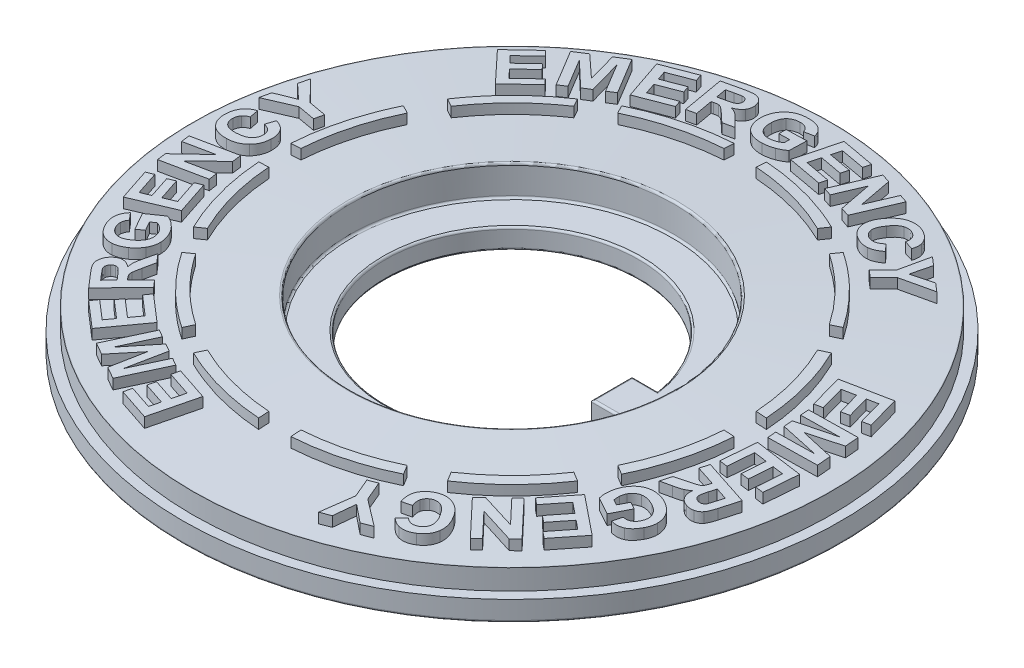
SolidWorks part; units mm, degrees
ref_plane "Front Plane" through (0, 0, 0) normal (0, 0, 1) x (1, 0, 0)
ref_plane "Top Plane" through (0, 0, 0) normal (0, 1, 0) x (1, 0, 0)
ref_plane "Right Plane" through (0, 0, 0) normal (1, 0, 0) x (0, 0, -1)
sketch "Sketch1" plane through (0, 0, 0) normal (0, 1, 0) x (1, 0, 0)
  circle A0 centre (0, 0) radius 12.5
  circle A1 centre (0, 0) radius 32.5
  dimension "D1" = 25
  dimension "D2" = 65
extrude "Boss-Extrude1" add sketch "Sketch1" along normal blind 2
sketch "Sketch2" plane through (0, 2, 0) normal (0, 1, 0) x (1, 0, 0)
  circle A1 centre (0, 0) radius 16
  circle A3 centre (0, 0) radius 31.5
  circle A4 centre (0, 0) radius 31.5
  dimension "D1" = 32
  dimension "D2" = 1
extrude "Boss-Extrude2" add sketch "Sketch2" along normal blind 3
sketch "Sketch3" plane through (0, 0, 0) normal (0, 0, 1) x (1, 0, 0)
  line L0 (15.9676, 5) -> (31.4687, 4)
  line L1 (16, 5) -> (-16, 5) construction
  line L2 (31.4687, 4) -> (33.9142, 4)
  line L3 (33.9142, 4) -> (33.9142, 6.9871)
  line L4 (33.9142, 6.9871) -> (15.9676, 6.9871)
  line L5 (15.9676, 6.9871) -> (15.9676, 5)
  line L6 (31.5, 5) -> (-31.5, 5) construction
  dimension "D1" = 1
revolve "Cut-Revolve1" cut sketch "Sketch3" angle 360 about axis through (0, 5, 0) along (0, -1, 0)
sketch "Sketch4" plane through (0, 0, 0) normal (0, -1, 0) x (1, 0, 0)
  line L0 (0, 0) -> (14.9309, 0) construction
  line L1 (12.339, 0) -> (12.339, -2) construction
  line L2 (12.339, 2) -> (13.461, 2)
  line L3 (12.339, -2) -> (9.839, -2)
  line L4 (13.461, 2) -> (13.461, -2)
  line L5 (12.339, 2) -> (9.839, 2)
  line L6 (9.839, -2) -> (9.839, 2)
  line L7 (13.461, -2) -> (12.339, -2)
  circle A0 centre (0, 0) radius 12.5 construction
  circle A1 centre (0, 0) radius 12.5 construction
  dimension "D1" = 2
  dimension "D2" = 4
  dimension "D3" = 2.5
extrude "Boss-Extrude3" add sketch "Sketch4" against normal up to surface (2 mm away) up to face at (0, 2, 12.5)
fillet "Fillet1" radius 0.2 12 edges at (0, 4, 31.4687) (0, 4.9979, -16) (11.089, 0, -2) (9.839, 0, 0) (11.089, 0, 2) (-12.5, 0, 0) (0, 0, 32.5) (0, 2, 16) (9.839, 2, 0) (11.089, 2, -2) (-12.5, 2, 0) (11.089, 2, 2)
sketch "Sketch5" plane through (0, 0, 0) normal (0, 1, 0) x (1, 0, 0)
  line L0 (-6.1951, -24.2972) -> (-7.6292, -28.6092)
  line L1 (-7.6292, -28.6092) -> (-10.8269, -27.5469)
  line L2 (-10.8269, -27.5469) -> (-10.5843, -26.8175)
  line L3 (-10.5843, -26.8175) -> (-8.2571, -27.5902)
  line L4 (-8.2571, -27.5902) -> (-7.9394, -26.635)
  line L5 (-7.9394, -26.635) -> (-10.1044, -25.9142)
  line L6 (-10.1044, -25.9142) -> (-9.8628, -25.1879)
  line L7 (-9.8628, -25.1879) -> (-7.6977, -25.9076)
  line L8 (-7.6977, -25.9076) -> (-7.3082, -24.7339)
  line L9 (-7.3082, -24.7339) -> (-9.7171, -23.933)
  line L10 (-9.7171, -23.933) -> (-9.4755, -23.2067)
  line L11 (-9.4755, -23.2067) -> (-6.1951, -24.2972)
  line L12 (-10.2124, -22.9447) -> (-12.4691, -26.8859)
  line L13 (-12.4691, -26.8859) -> (-13.6598, -26.2044)
  line L14 (-13.6598, -26.2044) -> (-12.8357, -23.1061)
  line L15 (-12.8357, -23.1061) -> (-15.0816, -25.3898)
  line L16 (-15.0816, -25.3898) -> (-16.2744, -24.7062)
  line L17 (-16.2744, -24.7062) -> (-14.0178, -20.7662)
  line L18 (-14.0178, -20.7662) -> (-13.2794, -21.1892)
  line L19 (-13.2794, -21.1892) -> (-15.055, -24.2913)
  line L20 (-15.055, -24.2913) -> (-12.4965, -21.6366)
  line L21 (-12.4965, -21.6366) -> (-11.7305, -22.0754)
  line L22 (-11.7305, -22.0754) -> (-12.7275, -25.6237)
  line L23 (-12.7275, -25.6237) -> (-10.9519, -22.5217)
  line L24 (-10.9519, -22.5217) -> (-10.2124, -22.9447)
  line L25 (-14.7736, -20.2293) -> (-17.7469, -23.6613)
  line L26 (-17.7469, -23.6613) -> (-20.2918, -21.457)
  line L27 (-20.2918, -21.457) -> (-19.7891, -20.8761)
  line L28 (-19.7891, -20.8761) -> (-17.9373, -22.4805)
  line L29 (-17.9373, -22.4805) -> (-17.2782, -21.7195)
  line L30 (-17.2782, -21.7195) -> (-19.0017, -20.2271)
  line L31 (-19.0017, -20.2271) -> (-18.5, -19.6483)
  line L32 (-18.5, -19.6483) -> (-16.7765, -21.1408)
  line L33 (-16.7765, -21.1408) -> (-15.9674, -20.207)
  line L34 (-15.9674, -20.207) -> (-17.8849, -18.5456)
  line L35 (-17.8849, -18.5456) -> (-17.3841, -17.9679)
  line L36 (-17.3841, -17.9679) -> (-14.7736, -20.2293)
  line L37 (-17.9353, -17.4044) -> (-21.3725, -20.3714)
  line L38 (-21.3725, -20.3714) -> (-22.6337, -18.9108)
  line L39 (-20.9108, -15.3133) -> (-20.6033, -14.3148)
  line L40 (-20.6033, -14.3148) -> (-19.8861, -15.1447)
  line L41 (-19.8861, -15.1447) -> (-20.2014, -16.2914)
  line L42 (-20.0907, -17.8082) -> (-19.9693, -17.9492)
  line L43 (-19.9693, -17.9492) -> (-18.5352, -16.7102)
  line L44 (-18.5352, -16.7102) -> (-17.9353, -17.4044)
  line L45 (-20.5183, -18.4224) -> (-20.9609, -17.9093)
  line L46 (-21.8574, -18.6338) -> (-21.3906, -19.1754)
  line L47 (-21.3906, -19.1754) -> (-20.5183, -18.4224)
  line L48 (-23.3127, -12.83) -> (-23.977, -13.2097)
  line L49 (-23.977, -13.2097) -> (-24.9571, -11.4924)
  line L50 (-24.9571, -11.4924) -> (-23.3849, -10.5967)
  line L51 (-25.6649, -11.9642) -> (-25.0651, -12.6712)
  line L52 (-23.3328, -11.6329) -> (-23.8329, -11.9178)
  line L53 (-23.8329, -11.9178) -> (-23.3127, -12.83)
  line L54 (-23.1179, -9.4693) -> (-27.4298, -10.895)
  line L55 (-27.4298, -10.895) -> (-28.4868, -7.6974)
  line L56 (-28.4868, -7.6974) -> (-27.7574, -7.4558)
  line L57 (-27.7574, -7.4558) -> (-26.9888, -9.7829)
  line L58 (-26.9888, -9.7829) -> (-26.0326, -9.4663)
  line L59 (-26.0326, -9.4663) -> (-26.748, -7.3014)
  line L60 (-26.748, -7.3014) -> (-26.0217, -7.0618)
  line L61 (-26.0217, -7.0618) -> (-25.3063, -9.2269)
  line L62 (-25.3063, -9.2269) -> (-24.1326, -8.8384)
  line L63 (-24.1326, -8.8384) -> (-24.9293, -6.4295)
  line L64 (-24.9293, -6.4295) -> (-24.2019, -6.189)
  line L65 (-24.2019, -6.189) -> (-23.1179, -9.4693)
  line L66 (-24.437, -5.4222) -> (-28.9431, -6.0107)
  line L67 (-28.9431, -6.0107) -> (-29.059, -5.1253)
  line L68 (-29.059, -5.1253) -> (-26.2903, -2.8879)
  line L69 (-26.2903, -2.8879) -> (-29.2997, -3.2817)
  line L70 (-29.2997, -3.2817) -> (-29.4102, -2.4354)
  line L71 (-29.4102, -2.4354) -> (-24.9041, -1.8469)
  line L72 (-24.9041, -1.8469) -> (-24.7849, -2.7598)
  line L73 (-24.7849, -2.7598) -> (-27.486, -4.961)
  line L74 (-27.486, -4.961) -> (-24.5476, -4.577)
  line L75 (-24.5476, -4.577) -> (-24.437, -5.4222)
  line L76 (-26.513, 2.089) -> (-26.2014, 2.9683)
  line L77 (-28.1029, 3.0201) -> (-27.9174, 2.1053)
  line L78 (-24.4491, 4.8765) -> (-26.3129, 5.3062)
  line L79 (-26.3129, 5.3062) -> (-29.2507, 4.2763)
  line L80 (-29.2507, 4.2763) -> (-29.0095, 5.324)
  line L81 (-29.0095, 5.324) -> (-27.0166, 5.9623)
  line L82 (-27.0166, 5.9623) -> (-28.5333, 7.3868)
  line L83 (-28.5333, 7.3868) -> (-28.2952, 8.4165)
  line L84 (-28.2952, 8.4165) -> (-26.1012, 6.1962)
  line L85 (-26.1012, 6.1962) -> (-24.2438, 5.7676)
  line L86 (-24.2438, 5.7676) -> (-24.4491, 4.8765)
  line L87 (-18.4634, 16.8285) -> (-21.5758, 20.1391)
  line L88 (-21.5758, 20.1391) -> (-19.1203, 22.4473)
  line L89 (-19.1203, 22.4473) -> (-18.5936, 21.8872)
  line L90 (-18.5936, 21.8872) -> (-20.3804, 20.2076)
  line L91 (-20.3804, 20.2076) -> (-19.6909, 19.4739)
  line L92 (-19.6909, 19.4739) -> (-18.0287, 21.0368)
  line L93 (-18.0287, 21.0368) -> (-17.5041, 20.4789)
  line L94 (-17.5041, 20.4789) -> (-19.1664, 18.9159)
  line L95 (-19.1664, 18.9159) -> (-18.3192, 18.015)
  line L96 (-18.3192, 18.015) -> (-16.4696, 19.7536)
  line L97 (-16.4696, 19.7536) -> (-15.945, 19.1956)
  line L98 (-15.945, 19.1956) -> (-18.4634, 16.8285)
  line L99 (-15.393, 19.7468) -> (-17.8185, 23.588)
  line L100 (-17.8185, 23.588) -> (-16.6575, 24.3209)
  line L101 (-16.6575, 24.3209) -> (-14.3069, 22.1408)
  line L102 (-14.3069, 22.1408) -> (-15.2712, 25.1954)
  line L103 (-15.2712, 25.1954) -> (-14.1081, 25.9306)
  line L104 (-14.1081, 25.9306) -> (-11.6825, 22.0894)
  line L105 (-11.6825, 22.0894) -> (-12.4038, 21.6344)
  line L106 (-12.4038, 21.6344) -> (-14.3123, 24.6575)
  line L107 (-14.3123, 24.6575) -> (-13.1665, 21.153)
  line L108 (-13.1665, 21.153) -> (-13.9132, 20.6811)
  line L109 (-13.9132, 20.6811) -> (-16.5823, 23.2251)
  line L110 (-16.5823, 23.2251) -> (-14.6728, 20.2018)
  line L111 (-14.6728, 20.2018) -> (-15.393, 19.7468)
  line L112 (-10.8729, 22.5268) -> (-12.502, 26.7677)
  line L113 (-12.502, 26.7677) -> (-9.3579, 27.9763)
  line L114 (-9.3579, 27.9763) -> (-9.0825, 27.2585)
  line L115 (-9.0825, 27.2585) -> (-11.3707, 26.3793)
  line L116 (-11.3707, 26.3793) -> (-11.0093, 25.4395)
  line L117 (-11.0093, 25.4395) -> (-8.8803, 26.2577)
  line L118 (-8.8803, 26.2577) -> (-8.6048, 25.5431)
  line L119 (-8.6048, 25.5431) -> (-10.7347, 24.7249)
  line L120 (-10.7347, 24.7249) -> (-10.2915, 23.5708)
  line L121 (-10.2915, 23.5708) -> (-7.9215, 24.4811)
  line L122 (-7.9215, 24.4811) -> (-7.6471, 23.7665)
  line L123 (-7.6471, 23.7665) -> (-10.8729, 22.5268)
  line L124 (-6.9043, 24.0185) -> (-7.918, 28.4456)
  line L125 (-7.918, 28.4456) -> (-6.0364, 28.8762)
  line L126 (-3.6626, 25.6705) -> (-2.9239, 24.9296)
  line L127 (-2.9239, 24.9296) -> (-3.9929, 24.6852)
  line L128 (-3.9929, 24.6852) -> (-4.8596, 25.5011)
  line L129 (-6.2523, 26.113) -> (-6.4334, 26.0717)
  line L130 (-6.4334, 26.0717) -> (-6.01, 24.2227)
  line L131 (-6.01, 24.2227) -> (-6.9043, 24.0185)
  line L132 (-6.5952, 26.7786) -> (-5.9338, 26.9299)
  line L133 (-6.1549, 28.0613) -> (-6.8524, 27.9015)
  line L134 (-6.8524, 27.9015) -> (-6.5952, 26.7786)
  line L135 (-0.3471, 26.653) -> (-0.3722, 27.418)
  line L136 (-0.3722, 27.418) -> (1.6033, 27.4821)
  line L137 (1.6033, 27.4821) -> (1.6619, 25.6727)
  line L138 (1.5173, 28.3281) -> (0.6119, 28.1285)
  line L139 (0.7208, 26.111) -> (0.7025, 26.6866)
  line L140 (0.7025, 26.6866) -> (-0.3471, 26.653)
  line L141 (2.5402, 24.9255) -> (3.3541, 29.3962)
  line L142 (3.3541, 29.3962) -> (6.6696, 28.7922)
  line L143 (6.6696, 28.7922) -> (6.5315, 28.0358)
  line L144 (6.5315, 28.0358) -> (4.1194, 28.476)
  line L145 (4.1194, 28.476) -> (3.9384, 27.4847)
  line L146 (3.9384, 27.4847) -> (6.1834, 27.0757)
  line L147 (6.1834, 27.0757) -> (6.0463, 26.3223)
  line L148 (6.0463, 26.3223) -> (3.8013, 26.7314)
  line L149 (3.8013, 26.7314) -> (3.5797, 25.5137)
  line L150 (3.5797, 25.5137) -> (6.0775, 25.0587)
  line L151 (6.0775, 25.0587) -> (5.9403, 24.3055)
  line L152 (5.9403, 24.3055) -> (2.5402, 24.9255)
  line L153 (6.711, 24.1235) -> (8.1441, 28.4356)
  line L154 (8.1441, 28.4356) -> (8.9911, 28.1544)
  line L155 (8.9911, 28.1544) -> (9.7993, 24.6873)
  line L156 (9.7993, 24.6873) -> (10.7564, 27.568)
  line L157 (10.7564, 27.568) -> (11.5654, 27.2982)
  line L158 (11.5654, 27.2982) -> (10.1313, 22.9862)
  line L159 (10.1313, 22.9862) -> (9.2576, 23.2768)
  line L160 (9.2576, 23.2768) -> (8.4541, 26.6666)
  line L161 (8.4541, 26.6666) -> (7.5199, 23.8548)
  line L162 (7.5199, 23.8548) -> (6.711, 24.1235)
  line L163 (14.3535, 22.5323) -> (14.9855, 21.8455)
  line L164 (15.9191, 23.5025) -> (15.0244, 23.7654)
  line L165 (15.8425, 19.3835) -> (17.0931, 20.8283)
  line L166 (17.0931, 20.8283) -> (17.5577, 23.9046)
  line L167 (17.5577, 23.9046) -> (18.3707, 23.2011)
  line L168 (18.3707, 23.2011) -> (18.0016, 21.143)
  line L169 (18.0016, 21.143) -> (19.97, 21.8153)
  line L170 (19.97, 21.8153) -> (20.7682, 21.1234)
  line L171 (20.7682, 21.1234) -> (17.7799, 20.225)
  line L172 (17.7799, 20.225) -> (16.5325, 18.7846)
  line L173 (16.5325, 18.7846) -> (15.8425, 19.3835)
  line L174 (23.6341, 8.518) -> (28.0103, 9.744)
  line L175 (28.0103, 9.744) -> (28.9196, 6.5001)
  line L176 (28.9196, 6.5001) -> (28.1793, 6.2924)
  line L177 (28.1793, 6.2924) -> (27.5175, 8.6531)
  line L178 (27.5175, 8.6531) -> (26.5474, 8.3815)
  line L179 (26.5474, 8.3815) -> (27.163, 6.1849)
  line L180 (27.163, 6.1849) -> (26.4259, 5.9783)
  line L181 (26.4259, 5.9783) -> (25.8102, 8.1748)
  line L182 (25.8102, 8.1748) -> (24.6188, 7.8413)
  line L183 (24.6188, 7.8413) -> (25.3036, 5.3969)
  line L184 (25.3036, 5.3969) -> (24.5665, 5.1903)
  line L185 (24.5665, 5.1903) -> (23.6341, 8.518)
  line L186 (24.8024, 4.4417) -> (29.332, 4.8102)
  line L187 (29.332, 4.8102) -> (29.443, 3.4425)
  line L188 (29.443, 3.4425) -> (26.4207, 2.3688)
  line L189 (26.4207, 2.3688) -> (29.5759, 1.807)
  line L190 (29.5759, 1.807) -> (29.688, 0.4351)
  line L191 (29.688, 0.4351) -> (25.1584, 0.0665)
  line L192 (25.1584, 0.0665) -> (25.0886, 0.917)
  line L193 (25.0886, 0.917) -> (28.6546, 1.2066)
  line L194 (28.6546, 1.2066) -> (25.0164, 1.8162)
  line L195 (25.0164, 1.8162) -> (24.9444, 2.6962)
  line L196 (24.9444, 2.6962) -> (28.437, 3.8829)
  line L197 (28.437, 3.8829) -> (24.8711, 3.5922)
  line L198 (24.8711, 3.5922) -> (24.8024, 4.4417)
  line L199 (25.0744, -0.851) -> (29.5986, -1.2269)
  line L200 (29.5986, -1.2269) -> (29.3198, -4.5823)
  line L201 (29.3198, -4.5823) -> (28.5551, -4.5183)
  line L202 (28.5551, -4.5183) -> (28.7573, -2.0769)
  line L203 (28.7573, -2.0769) -> (27.7545, -1.9935)
  line L204 (27.7545, -1.9935) -> (27.566, -4.2656)
  line L205 (27.566, -4.2656) -> (26.8033, -4.2017)
  line L206 (26.8033, -4.2017) -> (26.9918, -1.9305)
  line L207 (26.9918, -1.9305) -> (25.7606, -1.8277)
  line L208 (25.7606, -1.8277) -> (25.5503, -4.356)
  line L209 (25.5503, -4.356) -> (24.7876, -4.292)
  line L210 (24.7876, -4.292) -> (25.0744, -0.851)
  line L211 (24.6298, -5.0707) -> (29.0007, -6.3042)
  line L212 (29.0007, -6.3042) -> (28.4763, -8.1619)
  line L213 (24.5238, -8.7075) -> (23.5212, -9.0011)
  line L214 (23.5212, -9.0011) -> (23.819, -7.9451)
  line L215 (23.819, -7.9451) -> (24.9495, -7.576)
  line L216 (26.1547, -6.647) -> (26.205, -6.468)
  line L217 (26.205, -6.468) -> (24.3802, -5.954)
  line L218 (24.3802, -5.954) -> (24.6298, -5.0707)
  line L219 (26.903, -6.6652) -> (26.7184, -7.3186)
  line L220 (27.8178, -7.6672) -> (28.0129, -6.9777)
  line L221 (28.0129, -6.9777) -> (26.903, -6.6652)
  line L222 (23.8344, -12.1172) -> (24.5142, -12.468)
  line L223 (24.5142, -12.468) -> (23.6067, -14.225)
  line L224 (23.6067, -14.225) -> (21.9987, -13.394)
  line L225 (24.3881, -14.5621) -> (24.6545, -13.6747)
  line L226 (22.8392, -12.7863) -> (23.3519, -13.0507)
  line L227 (23.3519, -13.0507) -> (23.8344, -12.1172)
  line L228 (21.0017, -13.8427) -> (24.5624, -16.6606)
  line L229 (24.5624, -16.6606) -> (22.4731, -19.3005)
  line L230 (22.4731, -19.3005) -> (21.8702, -18.8236)
  line L231 (21.8702, -18.8236) -> (23.3912, -16.9028)
  line L232 (23.3912, -16.9028) -> (22.6013, -16.2772)
  line L233 (22.6013, -16.2772) -> (21.1865, -18.0649)
  line L234 (21.1865, -18.0649) -> (20.5867, -17.5901)
  line L235 (20.5867, -17.5901) -> (22.0016, -15.8024)
  line L236 (22.0016, -15.8024) -> (21.0332, -15.0356)
  line L237 (21.0332, -15.0356) -> (19.458, -17.0249)
  line L238 (19.458, -17.0249) -> (18.8583, -16.5502)
  line L239 (18.8583, -16.5502) -> (21.0017, -13.8427)
  line L240 (18.3331, -17.1447) -> (21.4454, -20.4563)
  line L241 (21.4454, -20.4563) -> (20.7947, -21.067)
  line L242 (20.7947, -21.067) -> (17.3611, -20.1304)
  line L243 (17.3611, -20.1304) -> (19.4392, -22.3409)
  line L244 (19.4392, -22.3409) -> (18.8184, -22.9254)
  line L245 (18.8184, -22.9254) -> (15.7061, -19.6137)
  line L246 (15.7061, -19.6137) -> (16.3769, -18.9831)
  line L247 (16.3769, -18.9831) -> (19.7409, -19.8875)
  line L248 (19.7409, -19.8875) -> (17.7111, -17.7291)
  line L249 (17.7111, -17.7291) -> (18.3331, -17.1447)
  line L250 (13.3532, -23.1592) -> (12.4501, -23.3963)
  line L251 (13.4769, -24.9983) -> (14.1285, -24.33)
  line L252 (9.8859, -23.0128) -> (10.5714, -24.7977)
  line L253 (10.5714, -24.7977) -> (13.0694, -26.6571)
  line L254 (13.0694, -26.6571) -> (12.0649, -27.0435)
  line L255 (12.0649, -27.0435) -> (10.4227, -25.7479)
  line L256 (10.4227, -25.7479) -> (10.0889, -27.8026)
  line L257 (10.0889, -27.8026) -> (9.1025, -28.1817)
  line L258 (9.1025, -28.1817) -> (9.7157, -25.1197)
  line L259 (9.7157, -25.1197) -> (9.0322, -23.3411)
  line L260 (9.0322, -23.3411) -> (9.8859, -23.0128)
  line L261 (-10.275, 21.0761) -> (-9.7743, 20.2088)
  line L262 (-1.513, 22.4187) -> (-1.513, 23.4207)
  line L263 (-19.4378, 13.0737) -> (-18.5693, 12.5723)
  line L264 (-12.5224, 18.6187) -> (-13.0236, 19.4867)
  line L265 (-23.3726, 1.5627) -> (-22.3702, 1.5627)
  line L266 (-20.16, 9.8245) -> (-21.0281, 10.3256)
  line L267 (-21.0264, -10.3743) -> (-20.1591, -9.8736)
  line L268 (-22.369, -1.6123) -> (-23.371, -1.6123)
  line L269 (-13.024, -19.5371) -> (-12.5226, -18.6686)
  line L270 (-18.569, -12.6217) -> (-19.437, -13.1229)
  line L271 (-1.513, -23.4719) -> (-1.513, -22.4695)
  line L272 (-9.7748, -20.2593) -> (-10.2759, -21.1274)
  line L273 (10.424, -21.1257) -> (9.9233, -20.2584)
  line L274 (1.662, -22.4683) -> (1.662, -23.4703)
  line L275 (19.5868, -13.1233) -> (18.7183, -12.6219)
  line L276 (12.6714, -18.6683) -> (13.1726, -19.5363)
  line L277 (23.5216, -1.6123) -> (22.5192, -1.6123)
  line L278 (20.309, -9.8741) -> (21.1771, -10.3752)
  line L279 (21.1763, 10.3252) -> (20.3086, 9.8242)
  line L280 (22.5186, 1.5627) -> (23.5204, 1.5627)
  line L281 (13.1724, 19.4864) -> (12.6714, 18.6186)
  line L282 (18.7181, 12.5722) -> (19.586, 13.0733)
  line L283 (1.662, 23.4207) -> (1.662, 22.4187)
  line L284 (9.9232, 20.2086) -> (10.4243, 21.0767)
  ellipse E0 centre (0.0745, -0.0248) end of major axis (0.0745, -25.0248) minor radius 25 construction
  spline S0 degree 3 poles (-22.6337, -18.9108) (-22.9506, -18.543) (-23.15, -18.2496) (-23.2322, -18.0304) knots 0.105263 0.105263 0.105263 0.105263 0.157895 0.157895 0.157895 0.157895
  spline S1 degree 3 poles (-23.2322, -18.0304) (-23.3133, -17.8101) (-23.3193, -17.5825) (-23.2479, -17.3466) knots 0.157895 0.157895 0.157895 0.157895 0.210526 0.210526 0.210526 0.210526
  spline S2 degree 3 poles (-23.2479, -17.3466) (-23.1756, -17.1097) (-23.0388, -16.9036) (-22.8352, -16.7282) knots 0.210526 0.210526 0.210526 0.210526 0.263158 0.263158 0.263158 0.263158
  spline S3 degree 3 poles (-22.8352, -16.7282) (-22.5776, -16.5064) (-22.2992, -16.3979) (-22.0007, -16.4047) knots 0.263158 0.263158 0.263158 0.263158 0.315789 0.315789 0.315789 0.315789
  spline S4 degree 3 poles (-22.0007, -16.4047) (-21.7012, -16.4116) (-21.3998, -16.5464) (-21.0955, -16.8106) knots 0.315789 0.315789 0.315789 0.315789 0.368421 0.368421 0.368421 0.368421
  spline S5 degree 3 poles (-21.0955, -16.8106) (-21.1374, -16.585) (-21.1487, -16.3776) (-21.1283, -16.1893) knots 0.368421 0.368421 0.368421 0.368421 0.421053 0.421053 0.421053 0.421053
  spline S6 degree 3 poles (-21.1283, -16.1893) (-21.1078, -16.0019) (-21.0354, -15.71) (-20.9108, -15.3133) knots 0.421053 0.421053 0.421053 0.421053 0.473684 0.473684 0.473684 0.473684
  spline S7 degree 3 poles (-20.2014, -16.2914) (-20.3153, -16.7007) (-20.3781, -16.9684) (-20.3911, -17.0933) knots 0.631579 0.631579 0.631579 0.631579 0.684211 0.684211 0.684211 0.684211
  spline S8 degree 3 poles (-20.3911, -17.0933) (-20.404, -17.2192) (-20.3915, -17.3304) (-20.3536, -17.4257) knots 0.684211 0.684211 0.684211 0.684211 0.736842 0.736842 0.736842 0.736842
  spline S9 degree 3 poles (-20.3536, -17.4257) (-20.3156, -17.521) (-20.228, -17.6491) (-20.0907, -17.8082) knots 0.736842 0.736842 0.736842 0.736842 0.789474 0.789474 0.789474 0.789474
  spline S10 degree 3 poles (-20.9609, -17.9093) (-21.2481, -17.5765) (-21.4425, -17.3804) (-21.5419, -17.322) knots 0.1 0.1 0.1 0.1 0.2 0.2 0.2 0.2
  spline S11 degree 3 poles (-21.5419, -17.322) (-21.6413, -17.2637) (-21.746, -17.2402) (-21.8551, -17.2527) knots 0.2 0.2 0.2 0.2 0.3 0.3 0.3 0.3
  spline S12 degree 3 poles (-21.8551, -17.2527) (-21.9641, -17.2652) (-22.07, -17.3158) (-22.1739, -17.4056) knots 0.3 0.3 0.3 0.3 0.4 0.4 0.4 0.4
  spline S13 degree 3 poles (-22.1739, -17.4056) (-22.2894, -17.5048) (-22.3563, -17.617) (-22.3734, -17.7397) knots 0.4 0.4 0.4 0.4 0.5 0.5 0.5 0.5
  spline S14 degree 3 poles (-22.3734, -17.7397) (-22.3916, -17.8625) (-22.3611, -17.9885) (-22.2831, -18.1177) knots 0.5 0.5 0.5 0.5 0.6 0.6 0.6 0.6
  spline S15 degree 3 poles (-22.2831, -18.1177) (-22.2419, -18.1802) (-22.1004, -18.3529) (-21.8574, -18.6338) knots 0.6 0.6 0.6 0.6 0.7 0.7 0.7 0.7
  spline S16 degree 3 poles (-23.3849, -10.5967) (-23.1289, -10.6713) (-22.8488, -10.8316) (-22.5444, -11.0777) knots 0.12 0.12 0.12 0.12 0.16 0.16 0.16 0.16
  spline S17 degree 3 poles (-22.5444, -11.0777) (-22.2411, -11.3249) (-21.9971, -11.6099) (-21.8115, -11.9353) knots 0.16 0.16 0.16 0.16 0.2 0.2 0.2 0.2
  spline S18 degree 3 poles (-21.8115, -11.9353) (-21.5762, -12.3473) (-21.4584, -12.7572) (-21.456, -13.1625) knots 0.2 0.2 0.2 0.2 0.24 0.24 0.24 0.24
  spline S19 degree 3 poles (-21.456, -13.1625) (-21.4545, -13.5678) (-21.5706, -13.9391) (-21.804, -14.2773) knots 0.24 0.24 0.24 0.24 0.28 0.28 0.28 0.28
  spline S20 degree 3 poles (-21.804, -14.2773) (-22.0386, -14.6155) (-22.3449, -14.8922) (-22.7231, -15.1085) knots 0.28 0.28 0.28 0.28 0.32 0.32 0.32 0.32
  spline S21 degree 3 poles (-22.7231, -15.1085) (-23.1342, -15.3428) (-23.5482, -15.4648) (-23.9663, -15.4746) knots 0.32 0.32 0.32 0.32 0.36 0.36 0.36 0.36
  spline S22 degree 3 poles (-23.9663, -15.4746) (-24.3833, -15.4844) (-24.7715, -15.3716) (-25.132, -15.137) knots 0.36 0.36 0.36 0.36 0.4 0.4 0.4 0.4
  spline S23 degree 3 poles (-25.132, -15.137) (-25.4068, -14.9587) (-25.6518, -14.682) (-25.867, -14.3049) knots 0.4 0.4 0.4 0.4 0.44 0.44 0.44 0.44
  spline S24 degree 3 poles (-25.867, -14.3049) (-26.1466, -13.8154) (-26.2612, -13.3739) (-26.2128, -12.9813) knots 0.44 0.44 0.44 0.44 0.48 0.48 0.48 0.48
  spline S25 degree 3 poles (-26.2128, -12.9813) (-26.1645, -12.5888) (-25.9818, -12.2494) (-25.6649, -11.9642) knots 0.48 0.48 0.48 0.48 0.52 0.52 0.52 0.52
  spline S26 degree 3 poles (-25.0651, -12.6712) (-25.2273, -12.8371) (-25.3207, -13.0285) (-25.3455, -13.2464) knots 0.56 0.56 0.56 0.56 0.6 0.6 0.6 0.6
  spline S27 degree 3 poles (-25.3455, -13.2464) (-25.3702, -13.4633) (-25.3167, -13.6867) (-25.1858, -13.9166) knots 0.6 0.6 0.6 0.6 0.64 0.64 0.64 0.64
  spline S28 degree 3 poles (-25.1858, -13.9166) (-24.9875, -14.2641) (-24.7191, -14.4784) (-24.3816, -14.5584) knots 0.64 0.64 0.64 0.64 0.68 0.68 0.68 0.68
  spline S29 degree 3 poles (-24.3816, -14.5584) (-24.0441, -14.6374) (-23.6577, -14.5534) (-23.2233, -14.3055) knots 0.68 0.68 0.68 0.68 0.72 0.72 0.72 0.72
  spline S30 degree 3 poles (-23.2233, -14.3055) (-22.7551, -14.0386) (-22.4635, -13.7342) (-22.3485, -13.3926) knots 0.72 0.72 0.72 0.72 0.76 0.76 0.76 0.76
  spline S31 degree 3 poles (-22.3485, -13.3926) (-22.2326, -13.051) (-22.2711, -12.7123) (-22.4631, -12.3743) knots 0.76 0.76 0.76 0.76 0.8 0.8 0.8 0.8
  spline S32 degree 3 poles (-22.4631, -12.3743) (-22.5591, -12.2079) (-22.6869, -12.0595) (-22.8475, -11.929) knots 0.8 0.8 0.8 0.8 0.84 0.84 0.84 0.84
  spline S33 degree 3 poles (-22.8475, -11.929) (-23.0093, -11.7986) (-23.171, -11.6999) (-23.3328, -11.6329) knots 0.84 0.84 0.84 0.84 0.88 0.88 0.88 0.88
  spline S34 degree 3 poles (-26.2014, 2.9683) (-25.7104, 2.8152) (-25.3504, 2.5752) (-25.1201, 2.2507) knots 0.052632 0.052632 0.052632 0.052632 0.105263 0.105263 0.105263 0.105263
  spline S35 degree 3 poles (-25.1201, 2.2507) (-24.8908, 1.9261) (-24.784, 1.5199) (-24.8004, 1.0322) knots 0.105263 0.105263 0.105263 0.105263 0.157895 0.157895 0.157895 0.157895
  spline S36 degree 3 poles (-24.8004, 1.0322) (-24.821, 0.429) (-25.0439, -0.0592) (-25.4691, -0.4327) knots 0.157895 0.157895 0.157895 0.157895 0.210526 0.210526 0.210526 0.210526
  spline S37 degree 3 poles (-25.4691, -0.4327) (-25.8943, -0.8072) (-26.464, -0.9827) (-27.1782, -0.9581) knots 0.210526 0.210526 0.210526 0.210526 0.263158 0.263158 0.263158 0.263158
  spline S38 degree 3 poles (-27.1782, -0.9581) (-27.9337, -0.9321) (-28.5141, -0.7169) (-28.9185, -0.3127) knots 0.263158 0.263158 0.263158 0.263158 0.315789 0.315789 0.315789 0.315789
  spline S39 degree 3 poles (-28.9185, -0.3127) (-29.3238, 0.0916) (-29.5155, 0.6117) (-29.4936, 1.2477) knots 0.315789 0.315789 0.315789 0.315789 0.368421 0.368421 0.368421 0.368421
  spline S40 degree 3 poles (-29.4936, 1.2477) (-29.4745, 1.8031) (-29.2953, 2.2484) (-28.9551, 2.5844) knots 0.368421 0.368421 0.368421 0.368421 0.421053 0.421053 0.421053 0.421053
  spline S41 degree 3 poles (-28.9551, 2.5844) (-28.7535, 2.7839) (-28.4698, 2.9287) (-28.1029, 3.0201) knots 0.421053 0.421053 0.421053 0.421053 0.473684 0.473684 0.473684 0.473684
  spline S42 degree 3 poles (-27.9174, 2.1053) (-28.1548, 2.0595) (-28.344, 1.9541) (-28.4861, 1.788) knots 0.526316 0.526316 0.526316 0.526316 0.578947 0.578947 0.578947 0.578947
  spline S43 degree 3 poles (-28.4861, 1.788) (-28.6282, 1.6229) (-28.7028, 1.4182) (-28.7121, 1.1749) knots 0.578947 0.578947 0.578947 0.578947 0.631579 0.631579 0.631579 0.631579
  spline S44 degree 3 poles (-28.7121, 1.1749) (-28.7232, 0.8373) (-28.611, 0.5602) (-28.3767, 0.3425) knots 0.631579 0.631579 0.631579 0.631579 0.684211 0.684211 0.684211 0.684211
  spline S45 degree 3 poles (-28.3767, 0.3425) (-28.1424, 0.1248) (-27.7549, 0.0074) (-27.2142, -0.0116) knots 0.684211 0.684211 0.684211 0.684211 0.736842 0.736842 0.736842 0.736842
  spline S46 degree 3 poles (-27.2142, -0.0116) (-26.6397, -0.0309) (-26.2283, 0.059) (-25.977, 0.257) knots 0.736842 0.736842 0.736842 0.736842 0.789474 0.789474 0.789474 0.789474
  spline S47 degree 3 poles (-25.977, 0.257) (-25.7268, 0.4552) (-25.5956, 0.7187) (-25.5845, 1.0499) knots 0.789474 0.789474 0.789474 0.789474 0.842105 0.842105 0.842105 0.842105
  spline S48 degree 3 poles (-25.5845, 1.0499) (-25.5762, 1.2932) (-25.6466, 1.5055) (-25.7955, 1.6866) knots 0.842105 0.842105 0.842105 0.842105 0.894737 0.894737 0.894737 0.894737
  spline S49 degree 3 poles (-25.7955, 1.6866) (-25.9444, 1.8666) (-26.1836, 2.0007) (-26.513, 2.089) knots 0.894737 0.894737 0.894737 0.894737 1 1 1 1
  spline S50 degree 3 poles (-6.0364, 28.8762) (-5.5633, 28.9852) (-5.2109, 29.0244) (-4.978, 28.9937) knots 0.105263 0.105263 0.105263 0.105263 0.157895 0.157895 0.157895 0.157895
  spline S51 degree 3 poles (-4.978, 28.9937) (-4.7452, 28.963) (-4.5409, 28.8614) (-4.3663, 28.6867) knots 0.157895 0.157895 0.157895 0.157895 0.210526 0.210526 0.210526 0.210526
  spline S52 degree 3 poles (-4.3663, 28.6867) (-4.1906, 28.5132) (-4.0732, 28.2951) (-4.0129, 28.0338) knots 0.210526 0.210526 0.210526 0.210526 0.263158 0.263158 0.263158 0.263158
  spline S53 degree 3 poles (-4.0129, 28.0338) (-3.9367, 27.7014) (-3.9716, 27.4051) (-4.1176, 27.1437) knots 0.263158 0.263158 0.263158 0.263158 0.315789 0.315789 0.315789 0.315789
  spline S54 degree 3 poles (-4.1176, 27.1437) (-4.2637, 26.8823) (-4.5241, 26.6791) (-4.8998, 26.5341) knots 0.315789 0.315789 0.315789 0.315789 0.368421 0.368421 0.368421 0.368421
  spline S55 degree 3 poles (-4.8998, 26.5341) (-4.6807, 26.4653) (-4.4923, 26.3785) (-4.3357, 26.2726) knots 0.368421 0.368421 0.368421 0.368421 0.421053 0.421053 0.421053 0.421053
  spline S56 degree 3 poles (-4.3357, 26.2726) (-4.1791, 26.1657) (-3.9547, 25.9658) (-3.6626, 25.6705) knots 0.421053 0.421053 0.421053 0.421053 0.473684 0.473684 0.473684 0.473684
  spline S57 degree 3 poles (-4.8596, 25.5011) (-5.1686, 25.7922) (-5.375, 25.9732) (-5.4798, 26.043) knots 0.631579 0.631579 0.631579 0.631579 0.684211 0.684211 0.684211 0.684211
  spline S58 degree 3 poles (-5.4798, 26.043) (-5.5855, 26.114) (-5.6893, 26.1541) (-5.7909, 26.1658) knots 0.684211 0.684211 0.684211 0.684211 0.736842 0.736842 0.736842 0.736842
  spline S59 degree 3 poles (-5.7909, 26.1658) (-5.8935, 26.1775) (-6.0471, 26.1606) (-6.2523, 26.113) knots 0.736842 0.736842 0.736842 0.736842 0.789474 0.789474 0.789474 0.789474
  spline S60 degree 3 poles (-5.9338, 26.9299) (-5.5052, 27.0284) (-5.2415, 27.1077) (-5.1432, 27.1681) knots 0.1 0.1 0.1 0.1 0.2 0.2 0.2 0.2
  spline S61 degree 3 poles (-5.1432, 27.1681) (-5.0447, 27.2284) (-4.9759, 27.3099) (-4.9358, 27.4125) knots 0.2 0.2 0.2 0.2 0.3 0.3 0.3 0.3
  spline S62 degree 3 poles (-4.9358, 27.4125) (-4.8955, 27.5152) (-4.8902, 27.6327) (-4.9209, 27.766) knots 0.3 0.3 0.3 0.3 0.4 0.4 0.4 0.4
  spline S63 degree 3 poles (-4.9209, 27.766) (-4.9548, 27.9142) (-5.0225, 28.0253) (-5.1231, 28.0994) knots 0.4 0.4 0.4 0.4 0.5 0.5 0.5 0.5
  spline S64 degree 3 poles (-5.1231, 28.0994) (-5.2236, 28.1724) (-5.3485, 28.2041) (-5.4998, 28.1957) knots 0.5 0.5 0.5 0.5 0.6 0.6 0.6 0.6
  spline S65 degree 3 poles (-5.4998, 28.1957) (-5.5739, 28.1894) (-5.7929, 28.1438) (-6.1549, 28.0613) knots 0.6 0.6 0.6 0.6 0.7 0.7 0.7 0.7
  spline S66 degree 3 poles (1.6619, 25.6727) (1.476, 25.4808) (1.2033, 25.3083) (0.8436, 25.1552) knots 0.12 0.12 0.12 0.12 0.16 0.16 0.16 0.16
  spline S67 degree 3 poles (0.8436, 25.1552) (0.4828, 25.0021) (0.1162, 24.9198) (-0.2573, 24.9074) knots 0.16 0.16 0.16 0.16 0.2 0.2 0.2 0.2
  spline S68 degree 3 poles (-0.2573, 24.9074) (-0.7324, 24.892) (-1.149, 24.9788) (-1.5082, 25.1665) knots 0.2 0.2 0.2 0.2 0.24 0.24 0.24 0.24
  spline S69 degree 3 poles (-1.5082, 25.1665) (-1.8684, 25.3542) (-2.1426, 25.6303) (-2.3318, 25.9951) knots 0.24 0.24 0.24 0.24 0.28 0.28 0.28 0.28
  spline S70 degree 3 poles (-2.3318, 25.9951) (-2.5219, 26.3598) (-2.6235, 26.7601) (-2.6375, 27.196) knots 0.28 0.28 0.28 0.28 0.32 0.32 0.32 0.32
  spline S71 degree 3 poles (-2.6375, 27.196) (-2.6527, 27.669) (-2.5672, 28.092) (-2.3807, 28.466) knots 0.32 0.32 0.32 0.32 0.36 0.36 0.36 0.36
  spline S72 degree 3 poles (-2.3807, 28.466) (-2.1942, 28.84) (-1.9138, 29.1311) (-1.5376, 29.3394) knots 0.36 0.36 0.36 0.36 0.4 0.4 0.4 0.4
  spline S73 degree 3 poles (-1.5376, 29.3394) (-1.252, 29.4993) (-0.8918, 29.5868) (-0.458, 29.6007) knots 0.4 0.4 0.4 0.4 0.44 0.44 0.44 0.44
  spline S74 degree 3 poles (-0.458, 29.6007) (0.1049, 29.6189) (0.5492, 29.5144) (0.8738, 29.2884) knots 0.44 0.44 0.44 0.44 0.48 0.48 0.48 0.48
  spline S75 degree 3 poles (0.8738, 29.2884) (1.1983, 29.0623) (1.4125, 28.7422) (1.5173, 28.3281) knots 0.48 0.48 0.48 0.48 0.52 0.52 0.52 0.52
  spline S76 degree 3 poles (0.6119, 28.1285) (0.5413, 28.3491) (0.4151, 28.5216) (0.2342, 28.6451) knots 0.56 0.56 0.56 0.56 0.6 0.6 0.6 0.6
  spline S77 degree 3 poles (0.2342, 28.6451) (0.0534, 28.7686) (-0.1683, 28.8262) (-0.4328, 28.8177) knots 0.6 0.6 0.6 0.6 0.64 0.64 0.64 0.64
  spline S78 degree 3 poles (-0.4328, 28.8177) (-0.8338, 28.804) (-1.1482, 28.6672) (-1.3758, 28.4051) knots 0.64 0.64 0.64 0.64 0.68 0.68 0.68 0.68
  spline S79 degree 3 poles (-1.3758, 28.4051) (-1.6045, 28.1439) (-1.7105, 27.7632) (-1.6939, 27.2638) knots 0.68 0.68 0.68 0.68 0.72 0.72 0.72 0.72
  spline S80 degree 3 poles (-1.6939, 27.2638) (-1.677, 26.7251) (-1.5437, 26.3251) (-1.2961, 26.0624) knots 0.72 0.72 0.72 0.72 0.76 0.76 0.76 0.76
  spline S81 degree 3 poles (-1.2961, 26.0624) (-1.0474, 25.8008) (-0.729, 25.6763) (-0.3417, 25.6889) knots 0.76 0.76 0.76 0.76 0.8 0.8 0.8 0.8
  spline S82 degree 3 poles (-0.3417, 25.6889) (-0.1492, 25.6957) (0.042, 25.7395) (0.233, 25.8204) knots 0.8 0.8 0.8 0.8 0.84 0.84 0.84 0.84
  spline S83 degree 3 poles (0.233, 25.8204) (0.4229, 25.9023) (0.5862, 25.9989) (0.7208, 26.111) knots 0.84 0.84 0.84 0.84 0.88 0.88 0.88 0.88
  spline S84 degree 3 poles (14.9855, 21.8455) (14.621, 21.4829) (14.2414, 21.2769) (13.8467, 21.2254) knots 0.052632 0.052632 0.052632 0.052632 0.105263 0.105263 0.105263 0.105263
  spline S85 degree 3 poles (13.8467, 21.2254) (13.4521, 21.1738) (13.0434, 21.2694) (12.6196, 21.511) knots 0.105263 0.105263 0.105263 0.105263 0.157895 0.157895 0.157895 0.157895
  spline S86 degree 3 poles (12.6196, 21.511) (12.0973, 21.8106) (11.7695, 22.2366) (11.6373, 22.7867) knots 0.157895 0.157895 0.157895 0.157895 0.210526 0.210526 0.210526 0.210526
  spline S87 degree 3 poles (11.6373, 22.7867) (11.5051, 23.3368) (11.6162, 23.9222) (11.9707, 24.542) knots 0.210526 0.210526 0.210526 0.210526 0.263158 0.263158 0.263158 0.263158
  spline S88 degree 3 poles (11.9707, 24.542) (12.3462, 25.1978) (12.808, 25.6103) (13.3538, 25.7796) knots 0.263158 0.263158 0.263158 0.263158 0.315789 0.315789 0.315789 0.315789
  spline S89 degree 3 poles (13.3538, 25.7796) (13.9007, 25.9478) (14.45, 25.8746) (15.0021, 25.5582) knots 0.315789 0.315789 0.315789 0.315789 0.368421 0.368421 0.368421 0.368421
  spline S90 degree 3 poles (15.0021, 25.5582) (15.484, 25.2828) (15.7937, 24.9162) (15.9321, 24.4592) knots 0.368421 0.368421 0.368421 0.368421 0.421053 0.421053 0.421053 0.421053
  spline S91 degree 3 poles (15.9321, 24.4592) (16.0142, 24.1873) (16.0105, 23.8687) (15.9191, 23.5025) knots 0.421053 0.421053 0.421053 0.421053 0.473684 0.473684 0.473684 0.473684
  spline S92 degree 3 poles (15.0244, 23.7654) (15.0948, 23.9962) (15.0891, 24.2132) (15.0094, 24.4163) knots 0.526316 0.526316 0.526316 0.526316 0.578947 0.578947 0.578947 0.578947
  spline S93 degree 3 poles (15.0094, 24.4163) (14.9296, 24.6182) (14.7833, 24.781) (14.5725, 24.9023) knots 0.578947 0.578947 0.578947 0.578947 0.631579 0.631579 0.631579 0.631579
  spline S94 degree 3 poles (14.5725, 24.9023) (14.28, 25.069) (13.9826, 25.1002) (13.6811, 24.9949) knots 0.631579 0.631579 0.631579 0.631579 0.684211 0.684211 0.684211 0.684211
  spline S95 degree 3 poles (13.6811, 24.9949) (13.3787, 24.8885) (13.0935, 24.6011) (12.8244, 24.1318) knots 0.684211 0.684211 0.684211 0.684211 0.736842 0.736842 0.736842 0.736842
  spline S96 degree 3 poles (12.8244, 24.1318) (12.5396, 23.6339) (12.426, 23.2273) (12.4838, 22.9131) knots 0.736842 0.736842 0.736842 0.736842 0.789474 0.789474 0.789474 0.789474
  spline S97 degree 3 poles (12.4838, 22.9131) (12.5425, 22.6) (12.7144, 22.36) (13.0015, 22.1965) knots 0.789474 0.789474 0.789474 0.789474 0.842105 0.842105 0.842105 0.842105
  spline S98 degree 3 poles (13.0015, 22.1965) (13.2134, 22.0751) (13.4336, 22.0385) (13.6621, 22.0855) knots 0.842105 0.842105 0.842105 0.842105 0.894737 0.894737 0.894737 0.894737
  spline S99 degree 3 poles (13.6621, 22.0855) (13.8917, 22.1325) (14.1222, 22.2811) (14.3535, 22.5323) knots 0.894737 0.894737 0.894737 0.894737 1 1 1 1
  spline S100 degree 3 poles (28.4763, -8.1619) (28.3452, -8.629) (28.2095, -8.9574) (28.0713, -9.1472) knots 0.105263 0.105263 0.105263 0.105263 0.157895 0.157895 0.157895 0.157895
  spline S101 degree 3 poles (28.0713, -9.1472) (27.9332, -9.3369) (27.7462, -9.4666) (27.5093, -9.537) knots 0.157895 0.157895 0.157895 0.157895 0.210526 0.210526 0.210526 0.210526
  spline S102 degree 3 poles (27.5093, -9.537) (27.2725, -9.6074) (27.0247, -9.607) (26.7664, -9.5336) knots 0.210526 0.210526 0.210526 0.210526 0.263158 0.263158 0.263158 0.263158
  spline S103 degree 3 poles (26.7664, -9.5336) (26.439, -9.4413) (26.1952, -9.2683) (26.0358, -9.0147) knots 0.263158 0.263158 0.263158 0.263158 0.315789 0.315789 0.315789 0.315789
  spline S104 degree 3 poles (26.0358, -9.0147) (25.8765, -8.7622) (25.8227, -8.4364) (25.8757, -8.0362) knots 0.315789 0.315789 0.315789 0.315789 0.368421 0.368421 0.368421 0.368421
  spline S105 degree 3 poles (25.8757, -8.0362) (25.7109, -8.1965) (25.544, -8.3185) (25.376, -8.4058) knots 0.368421 0.368421 0.368421 0.368421 0.421053 0.421053 0.421053 0.421053
  spline S106 degree 3 poles (25.376, -8.4058) (25.2068, -8.4919) (24.9235, -8.5932) (24.5238, -8.7075) knots 0.421053 0.421053 0.421053 0.421053 0.473684 0.473684 0.473684 0.473684
  spline S107 degree 3 poles (24.9495, -7.576) (25.3534, -7.4449) (25.6114, -7.35) (25.7234, -7.2915) knots 0.631579 0.631579 0.631579 0.631579 0.684211 0.684211 0.684211 0.684211
  spline S108 degree 3 poles (25.7234, -7.2915) (25.8355, -7.233) (25.921, -7.1619) (25.9801, -7.0781) knots 0.684211 0.684211 0.684211 0.684211 0.736842 0.736842 0.736842 0.736842
  spline S109 degree 3 poles (25.9801, -7.0781) (26.0392, -6.9934) (26.098, -6.8503) (26.1547, -6.647) knots 0.736842 0.736842 0.736842 0.736842 0.789474 0.789474 0.789474 0.789474
  spline S110 degree 3 poles (26.7184, -7.3186) (26.5998, -7.7412) (26.5423, -8.0113) (26.549, -8.1266) knots 0.1 0.1 0.1 0.1 0.2 0.2 0.2 0.2
  spline S111 degree 3 poles (26.549, -8.1266) (26.5546, -8.2419) (26.5929, -8.3424) (26.6641, -8.4268) knots 0.2 0.2 0.2 0.2 0.3 0.3 0.3 0.3
  spline S112 degree 3 poles (26.6641, -8.4268) (26.7341, -8.5102) (26.8359, -8.5714) (26.9661, -8.6081) knots 0.3 0.3 0.3 0.3 0.4 0.4 0.4 0.4
  spline S113 degree 3 poles (26.9661, -8.6081) (27.1134, -8.65) (27.2435, -8.6445) (27.3566, -8.5913) knots 0.4 0.4 0.4 0.4 0.5 0.5 0.5 0.5
  spline S114 degree 3 poles (27.3566, -8.5913) (27.4687, -8.5381) (27.5573, -8.4436) (27.6215, -8.3069) knots 0.5 0.5 0.5 0.5 0.6 0.6 0.6 0.6
  spline S115 degree 3 poles (27.6215, -8.3069) (27.652, -8.238) (27.7171, -8.0251) (27.8178, -7.6672) knots 0.6 0.6 0.6 0.6 0.7 0.7 0.7 0.7
  spline S116 degree 3 poles (21.9987, -13.394) (21.9219, -13.1389) (21.9036, -12.816) (21.9456, -12.4266) knots 0.12 0.12 0.12 0.12 0.16 0.16 0.16 0.16
  spline S117 degree 3 poles (21.9456, -12.4266) (21.9866, -12.0383) (22.0933, -11.6776) (22.2654, -11.3457) knots 0.16 0.16 0.16 0.16 0.2 0.2 0.2 0.2
  spline S118 degree 3 poles (22.2654, -11.3457) (22.4832, -10.9228) (22.7623, -10.6006) (23.1013, -10.378) knots 0.2 0.2 0.2 0.2 0.24 0.24 0.24 0.24
  spline S119 degree 3 poles (23.1013, -10.378) (23.4405, -10.1554) (23.8154, -10.0503) (24.2271, -10.0628) knots 0.24 0.24 0.24 0.24 0.28 0.28 0.28 0.28
  spline S120 degree 3 poles (24.2271, -10.0628) (24.6377, -10.0753) (25.0374, -10.182) (25.4244, -10.3818) knots 0.28 0.28 0.28 0.28 0.32 0.32 0.32 0.32
  spline S121 degree 3 poles (25.4244, -10.3818) (25.8452, -10.5985) (26.1727, -10.8797) (26.408, -11.2251) knots 0.32 0.32 0.32 0.32 0.36 0.36 0.36 0.36
  spline S122 degree 3 poles (26.408, -11.2251) (26.6443, -11.5696) (26.7621, -11.9572) (26.7601, -12.3869) knots 0.36 0.36 0.36 0.36 0.4 0.4 0.4 0.4
  spline S123 degree 3 poles (26.7601, -12.3869) (26.7605, -12.715) (26.6613, -13.0715) (26.4626, -13.4573) knots 0.4 0.4 0.4 0.4 0.44 0.44 0.44 0.44
  spline S124 degree 3 poles (26.4626, -13.4573) (26.2033, -13.9584) (25.8957, -14.2954) (25.5408, -14.4693) knots 0.44 0.44 0.44 0.44 0.48 0.48 0.48 0.48
  spline S125 degree 3 poles (25.5408, -14.4693) (25.1848, -14.6421) (24.8006, -14.6731) (24.3881, -14.5621) knots 0.48 0.48 0.48 0.48 0.52 0.52 0.52 0.52
  spline S126 degree 3 poles (24.6545, -13.6747) (24.8819, -13.7207) (25.0936, -13.6937) (25.2897, -13.5967) knots 0.56 0.56 0.56 0.56 0.6 0.6 0.6 0.6
  spline S127 degree 3 poles (25.2897, -13.5967) (25.4857, -13.4987) (25.6448, -13.3329) (25.7659, -13.0971) knots 0.6 0.6 0.6 0.6 0.64 0.64 0.64 0.64
  spline S128 degree 3 poles (25.7659, -13.0971) (25.9497, -12.7408) (25.9833, -12.4001) (25.8654, -12.0728) knots 0.64 0.64 0.64 0.64 0.68 0.68 0.68 0.68
  spline S129 degree 3 poles (25.8654, -12.0728) (25.7486, -11.7466) (25.4677, -11.4677) (25.0237, -11.2392) knots 0.68 0.68 0.68 0.68 0.72 0.72 0.72 0.72
  spline S130 degree 3 poles (25.0237, -11.2392) (24.5447, -10.9916) (24.13, -10.9124) (23.7806, -11.0017) knots 0.72 0.72 0.72 0.72 0.76 0.76 0.76 0.76
  spline S131 degree 3 poles (23.7806, -11.0017) (23.4312, -11.0909) (23.1672, -11.3074) (22.9886, -11.653) knots 0.76 0.76 0.76 0.76 0.8 0.8 0.8 0.8
  spline S132 degree 3 poles (22.9886, -11.653) (22.9005, -11.8232) (22.8461, -12.0115) (22.8245, -12.2179) knots 0.8 0.8 0.8 0.8 0.84 0.84 0.84 0.84
  spline S133 degree 3 poles (22.8245, -12.2179) (22.8029, -12.4242) (22.8078, -12.6137) (22.8392, -12.7863) knots 0.84 0.84 0.84 0.84 0.88 0.88 0.88 0.88
  spline S134 degree 3 poles (12.4501, -23.3963) (12.3016, -22.9043) (12.2957, -22.4714) (12.4354, -22.0987) knots 0.052632 0.052632 0.052632 0.052632 0.105263 0.105263 0.105263 0.105263
  spline S135 degree 3 poles (12.4354, -22.0987) (12.5752, -21.7259) (12.8512, -21.4089) (13.2634, -21.1489) knots 0.105263 0.105263 0.105263 0.105263 0.157895 0.157895 0.157895 0.157895
  spline S136 degree 3 poles (13.2634, -21.1489) (13.7743, -20.8269) (14.3029, -20.7369) (14.8514, -20.8777) knots 0.157895 0.157895 0.157895 0.157895 0.210526 0.210526 0.210526 0.210526
  spline S137 degree 3 poles (14.8514, -20.8777) (15.3999, -21.0184) (15.8655, -21.3916) (16.2472, -21.996) knots 0.210526 0.210526 0.210526 0.210526 0.263158 0.263158 0.263158 0.263158
  spline S138 degree 3 poles (16.2472, -21.996) (16.6509, -22.6356) (16.7987, -23.2364) (16.6918, -23.7989) knots 0.263158 0.263158 0.263158 0.263158 0.315789 0.315789 0.315789 0.315789
  spline S139 degree 3 poles (16.6918, -23.7989) (16.5847, -24.3603) (16.2625, -24.8113) (15.725, -25.1511) knots 0.315789 0.315789 0.315789 0.315789 0.368421 0.368421 0.368421 0.368421
  spline S140 degree 3 poles (15.725, -25.1511) (15.2544, -25.4479) (14.785, -25.5499) (14.3167, -25.4572) knots 0.368421 0.368421 0.368421 0.368421 0.421053 0.421053 0.421053 0.421053
  spline S141 degree 3 poles (14.3167, -25.4572) (14.0386, -25.4037) (13.7579, -25.2507) (13.4769, -24.9983) knots 0.421053 0.421053 0.421053 0.421053 0.473684 0.473684 0.473684 0.473684
  spline S142 degree 3 poles (14.1285, -24.33) (14.3, -24.5004) (14.4942, -24.5978) (14.7109, -24.6224) knots 0.526316 0.526316 0.526316 0.526316 0.578947 0.578947 0.578947 0.578947
  spline S143 degree 3 poles (14.7109, -24.6224) (14.9278, -24.6469) (15.1397, -24.5942) (15.3459, -24.4642) knots 0.578947 0.578947 0.578947 0.578947 0.631579 0.631579 0.631579 0.631579
  spline S144 degree 3 poles (15.3459, -24.4642) (15.6305, -24.2838) (15.7971, -24.036) (15.8445, -23.7198) knots 0.631579 0.631579 0.631579 0.631579 0.684211 0.684211 0.684211 0.684211
  spline S145 degree 3 poles (15.8445, -23.7198) (15.8928, -23.4026) (15.7724, -23.0156) (15.484, -22.5589) knots 0.684211 0.684211 0.684211 0.684211 0.736842 0.736842 0.736842 0.736842
  spline S146 degree 3 poles (15.484, -22.5589) (15.1778, -22.0724) (14.8715, -21.7816) (14.5673, -21.6856) knots 0.736842 0.736842 0.736842 0.736842 0.789474 0.789474 0.789474 0.789474
  spline S147 degree 3 poles (14.5673, -21.6856) (14.262, -21.5907) (13.9696, -21.6304) (13.6903, -21.8076) knots 0.789474 0.789474 0.789474 0.789474 0.842105 0.842105 0.842105 0.842105
  spline S148 degree 3 poles (13.6903, -21.8076) (13.4841, -21.9376) (13.3477, -22.1145) (13.2828, -22.3396) knots 0.842105 0.842105 0.842105 0.842105 0.894737 0.894737 0.894737 0.894737
  spline S149 degree 3 poles (13.2828, -22.3396) (13.2169, -22.5647) (13.2397, -22.8379) (13.3532, -23.1592) knots 0.894737 0.894737 0.894737 0.894737 1 1 1 1
  spline S150 degree 3 poles (-1.513, 23.4207) (-4.641, 23.212) (-7.6008, 22.39) (-10.275, 21.0761) knots 0 0 0 0 0.2 0.2 0.2 0.2
  spline S151 degree 3 poles (-9.7743, 20.2088) (-7.2491, 21.4401) (-4.4593, 22.2133) (-1.513, 22.4187) knots 0.4 0.4 0.4 0.4 0.6 0.6 0.6 0.6
  spline S152 degree 3 poles (-13.0236, 19.4867) (-15.5543, 17.785) (-17.7355, 15.6038) (-19.4378, 13.0737) knots 0 0 0 0 0.2 0.2 0.2 0.2
  spline S153 degree 3 poles (-18.5693, 12.5723) (-16.9577, 14.9522) (-14.9027, 17.0075) (-12.5224, 18.6187) knots 0.4 0.4 0.4 0.4 0.6 0.6 0.6 0.6
  spline S154 degree 3 poles (-21.0281, 10.3256) (-22.3426, 7.6515) (-23.1638, 4.691) (-23.3726, 1.5627) knots 0 0 0 0 0.2 0.2 0.2 0.2
  spline S155 degree 3 poles (-22.3702, 1.5627) (-22.1648, 4.5093) (-21.3919, 7.2994) (-20.16, 9.8245) knots 0.4 0.4 0.4 0.4 0.6 0.6 0.6 0.6
  spline S156 degree 3 poles (-23.371, -1.6123) (-23.1623, -4.7403) (-22.3403, -7.7001) (-21.0264, -10.3743) knots 0 0 0 0 0.2 0.2 0.2 0.2
  spline S157 degree 3 poles (-20.1591, -9.8736) (-21.3904, -7.3484) (-22.1636, -4.5586) (-22.369, -1.6123) knots 0.4 0.4 0.4 0.4 0.6 0.6 0.6 0.6
  spline S158 degree 3 poles (-19.437, -13.1229) (-17.7353, -15.6536) (-15.5541, -17.8348) (-13.024, -19.5371) knots 0 0 0 0 0.2 0.2 0.2 0.2
  spline S159 degree 3 poles (-12.5226, -18.6686) (-14.9025, -17.057) (-16.9578, -15.002) (-18.569, -12.6217) knots 0.4 0.4 0.4 0.4 0.6 0.6 0.6 0.6
  spline S160 degree 3 poles (-10.2759, -21.1274) (-7.6018, -22.4419) (-4.6413, -23.2631) (-1.513, -23.4719) knots 0 0 0 0 0.2 0.2 0.2 0.2
  spline S161 degree 3 poles (-1.513, -22.4695) (-4.4596, -22.2641) (-7.2497, -21.4912) (-9.7748, -20.2593) knots 0.4 0.4 0.4 0.4 0.6 0.6 0.6 0.6
  spline S162 degree 3 poles (1.662, -23.4703) (4.79, -23.2616) (7.7498, -22.4396) (10.424, -21.1257) knots 0 0 0 0 0.2 0.2 0.2 0.2
  spline S163 degree 3 poles (9.9233, -20.2584) (7.3981, -21.4897) (4.6083, -22.2629) (1.662, -22.4683) knots 0.4 0.4 0.4 0.4 0.6 0.6 0.6 0.6
  spline S164 degree 3 poles (13.1726, -19.5363) (15.7033, -17.8346) (17.8845, -15.6534) (19.5868, -13.1233) knots 0 0 0 0 0.2 0.2 0.2 0.2
  spline S165 degree 3 poles (18.7183, -12.6219) (17.1067, -15.0018) (15.0517, -17.0571) (12.6714, -18.6683) knots 0.4 0.4 0.4 0.4 0.6 0.6 0.6 0.6
  spline S166 degree 3 poles (21.1771, -10.3752) (22.4916, -7.7011) (23.3128, -4.7406) (23.5216, -1.6123) knots 0 0 0 0 0.2 0.2 0.2 0.2
  spline S167 degree 3 poles (22.5192, -1.6123) (22.3138, -4.5589) (21.5409, -7.349) (20.309, -9.8741) knots 0.4 0.4 0.4 0.4 0.6 0.6 0.6 0.6
  spline S168 degree 3 poles (23.5204, 1.5627) (23.3117, 4.6908) (22.4905, 7.651) (21.1763, 10.3252) knots 0 0 0 0 0.2 0.2 0.2 0.2
  spline S169 degree 3 poles (20.3086, 9.8242) (21.5401, 7.299) (22.3132, 4.5092) (22.5186, 1.5627) knots 0.4 0.4 0.4 0.4 0.6 0.6 0.6 0.6
  spline S170 degree 3 poles (19.586, 13.0733) (17.8841, 15.6036) (15.7026, 17.7844) (13.1724, 19.4864) knots 0 0 0 0 0.2 0.2 0.2 0.2
  spline S171 degree 3 poles (12.6714, 18.6186) (15.0514, 17.0072) (17.1067, 14.9523) (18.7181, 12.5722) knots 0.4 0.4 0.4 0.4 0.6 0.6 0.6 0.6
  spline S172 degree 3 poles (10.4243, 21.0767) (7.7503, 22.391) (4.79, 23.212) (1.662, 23.4207) knots 0 0 0 0 0.2 0.2 0.2 0.2
  spline S173 degree 3 poles (1.662, 22.4187) (4.6084, 22.2133) (7.3982, 21.4402) (9.9232, 20.2086) knots 0.4 0.4 0.4 0.4 0.6 0.6 0.6 0.6
extrude "Boss-Extrude4" add sketch "Sketch5" along normal blind 7
sketch "Sketch6" plane through (0, 0, 0) normal (1, 0, 0) x (0, 0, -1)
  line L0 (11.2572, 4.9846) -> (0, 4.9846) construction
  line L1 (16.2, 4.9846) -> (-16.2, 4.9846) construction
  line L2 (0, 4.9846) -> (-33.1781, 4.9846) construction
  line L3 (0, 4.9846) -> (0, 6.9846) construction
  line L4 (0, 4.0004) -> (0, 4.9842) construction
  line L5 (-31.5, 4) -> (-31.5, 5) construction
  line L6 (-31.5, 5) -> (0, 6.9846)
  line L7 (0, 6.9846) -> (0, 8.6894)
  line L8 (0, 8.6894) -> (-31.5, 8.6894)
  line L9 (-31.5, 8.6894) -> (-31.5, 5)
  dimension "D1" = 2
  dimension "D2" = 1
revolve "Cut-Revolve2" cut sketch "Sketch6" angle 360 about axis through (0, 5, 0) along (0, -1, 0)
sketch "Sketch7" plane through (0, 0, 0) normal (0, -1, 0) x (1, 0, 0)
  line L0 (10.939, 0.9) -> (10.939, -0.9) construction
  line L1 (10.039, 0) -> (11.839, 0) construction
  line L2 (10.039, 1.8) -> (10.039, -1.8) construction
  line L4 (11.339, -0.5) -> (10.539, -0.5)
  line L5 (11.339, -0.5) -> (11.339, -1.3)
  line L6 (11.339, -1.3) -> (10.539, -1.3)
  line L7 (10.539, -0.5) -> (10.539, -1.3)
  line L8 (11.339, -0.5) -> (10.539, -1.3) construction
  line L9 (11.339, -1.3) -> (10.539, -0.5) construction
  line L10 (11.339, 1.3) -> (10.539, 1.3)
  line L11 (11.339, 1.3) -> (11.339, 0.5)
  line L12 (11.339, 0.5) -> (10.539, 0.5)
  line L13 (10.539, 1.3) -> (10.539, 0.5)
  line L14 (11.339, 1.3) -> (10.539, 0.5) construction
  line L15 (11.339, 0.5) -> (10.539, 1.3) construction
  point P3 (10.939, 0)
  dimension "D1" = 1.8
  dimension "D2" = 0.8
  dimension "D3" = 0.8
  dimension "D4" = 1.8
extrude "Boss-Extrude5" add sketch "Sketch7" along normal blind 3.5 separate body
sketch "Sketch8" plane through (0, -3.5, 0) normal (0, -1, 0) x (1, 0, 0)
  line L4 (10.539, -0.5) -> (10.539, -1.3)
  line L5 (10.539, -1.3) -> (11.339, -1.3)
  line L6 (11.339, -1.3) -> (11.339, -0.5)
  line L7 (11.339, -0.5) -> (10.539, -0.5)
  line L8 (10.539, -0.5) -> (10.539, -1.3)
  line L9 (10.539, -1.3) -> (11.339, -1.3)
  line L10 (11.339, -1.3) -> (11.339, -0.5)
  line L11 (11.339, -0.5) -> (10.539, -0.5)
  line L12 (10.539, 1.3) -> (10.539, 0.5)
  line L13 (10.539, 0.5) -> (11.339, 0.5)
  line L14 (11.339, 0.5) -> (11.339, 1.3)
  line L15 (11.339, 1.3) -> (10.539, 1.3)
  line L16 (10.539, 1.3) -> (10.539, 0.5)
  line L17 (10.539, 0.5) -> (11.339, 0.5)
  line L18 (11.339, 0.5) -> (11.339, 1.3)
  line L19 (11.339, 1.3) -> (10.539, 1.3)
  dimension "D1" = 0
  dimension "D2" = 0
extrude "Boss-Extrude6" add sketch "Sketch8" along normal blind 2 draft 45
sketch "Sketch9" plane through (0, 0, 0) normal (0, -1, 0) x (1, 0, 0)
  line L0 (0, -7.5181) -> (0, 7.5181) construction
  circle A1 centre (0, -0.2292) radius 14.5
  circle A3 centre (0, -0.2292) radius 13.5
  dimension "D2" = 29
  dimension "D4" = 27
